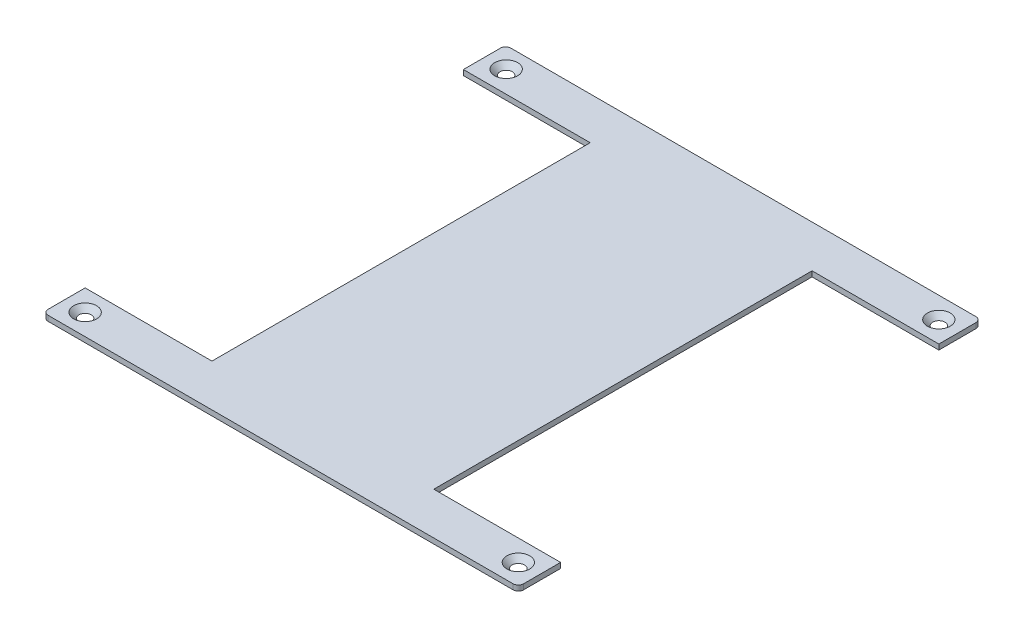
SolidWorks part; units mm, degrees
material "7075-T6, Plate (SS)"
ref_plane "Front Plane" through (0, 0, 0) normal (0, 0, 1) x (1, 0, 0)
ref_plane "Top Plane" through (0, 0, 0) normal (0, 1, 0) x (1, 0, 0)
ref_plane "Right Plane" through (0, 0, 0) normal (1, 0, 0) x (0, 0, -1)
sketch "Sketch1" plane through (0, 0, 0) normal (0, 1, 0) x (1, 0, 0)
  line L1 (-70.2264, 30.9547) -> (44.0736, 30.9547)
  line L2 (-70.2264, 30.9547) -> (-70.2264, -80.2973)
  line L3 (-70.2264, -80.2973) -> (44.0736, -80.2973)
  line L4 (44.0736, 30.9547) -> (44.0736, -80.2973)
  dimension "D1" = 114.3
  dimension "D2" = 111.252
extrude "Boss-Extrude1" add sketch "Sketch1" along normal blind 1.27
hole_wizard "CSK for M2.5 Countersunk Flat Head Screw1" positions "Sketch2" profile "Sketch3" countersink size "M2.5" standard "ISO" end condition up to next
sketch "Sketch2" plane through (0, 1.27, 0) normal (0, 1, 0) x (1, 0, 0)
  line L0 (44.0736, 30.9547) -> (-70.2264, 30.9547) construction
  line L1 (-70.2264, 30.9547) -> (-70.2264, -80.2973) construction
  line L2 (44.0736, -80.2973) -> (44.0736, 30.9547) construction
  line L3 (-70.2264, -80.2973) -> (44.0736, -80.2973) construction
  point P0 (-65.1464, 26.0017)
  point P2 (38.9936, 25.8747)
  point P4 (38.9936, -75.2173)
  point P6 (-65.1464, -75.2173)
  dimension "D1" = 4.953
  dimension "D2" = 5.08
  dimension "D3" = 5.08
  dimension "D4" = 5.08
  dimension "D5" = 5.08
  dimension "D6" = 5.08
  dimension "D7" = 5.08
  dimension "D8" = 5.08
sketch "Sketch3" plane through (-65.1464, 1.27, -26.0017) normal (1, 0, 0) x (0, 0, 1)
  line L0 (0, 0) -> (0, 1.27)
  line L1 (0, 1.27) -> (1.45, 1.27)
  line L2 (1.45, 1.27) -> (1.45, 1.3)
  line L3 (1.45, 1.3) -> (2.75, 0)
  line L5 (2.75, 0) -> (0, 0)
  line L6 (-1.45, 1.3) -> (-2.75, 0) construction
  line L11 (0, -6.35) -> (0, 107.95) construction
  dimension "Thru Hole Dia." = 2.9
  dimension "Thru Hole Depth" = 1.27
  dimension "Near C'Sink Dia." = 5.5
  dimension "Near C'Sink Angle" = 90
fillet "Fillet1" radius 1.27 4 edges at (-70.2264, 0.635, 80.2973) (44.0736, 0.635, 80.2973) (44.0736, 0.635, -30.9547) (-70.2264, 0.635, -30.9547)
sketch "Sketch4" plane through (0, 1.27, 0) normal (0, 1, 0) x (1, 0, 0)
  line L0 (-70.2264, 30.9547) -> (-38.8226, 30.9547)
  line L1 (-70.2264, 29.6847) -> (-70.2264, -79.0273) construction
  line L2 (-38.8226, 30.9547) -> (-38.8226, -80.2973)
  line L3 (-38.8226, -80.2973) -> (-70.2264, -80.2973)
  line L4 (-70.2264, -80.2973) -> (-70.2264, 30.9547)
  line L5 (42.8036, 30.9547) -> (-68.9564, 30.9547) construction
  line L6 (-68.9564, -80.2973) -> (42.8036, -80.2973) construction
  dimension "D1" = 0
  dimension "D2" = 0
sketch "Sketch9" plane through (0, 1.27, 0) normal (0, 1, 0) x (1, 0, 0)
  line L0 (44.0736, 20.7947) -> (13.5936, 20.7947)
  line L1 (44.0736, -79.0273) -> (44.0736, 29.6847) construction
  line L2 (13.5936, 20.7947) -> (13.5936, -70.1373)
  line L3 (13.5936, -70.1373) -> (44.0736, -70.1373)
  line L4 (44.0736, -70.1373) -> (44.0736, 20.7947)
  line L5 (-68.9564, -80.2973) -> (42.8036, -80.2973) construction
  line L6 (42.8036, 30.9547) -> (-68.9564, 30.9547) construction
  line L7 (-13.0764, -80.2973) -> (-13.0764, 30.9547) construction
  line L8 (-39.7464, -70.1373) -> (-70.2264, -70.1373)
  line L9 (-70.2264, -70.1373) -> (-70.2264, 20.7947)
  line L10 (-39.7464, 20.7947) -> (-39.7464, -70.1373)
  line L11 (-70.2264, 20.7947) -> (-39.7464, 20.7947)
  dimension "D1" = 10.16
  dimension "D2" = 10.16
  dimension "D3" = 30.48
extrude "Cut-Extrude5" cut sketch "Sketch9" against normal blind 5.08
